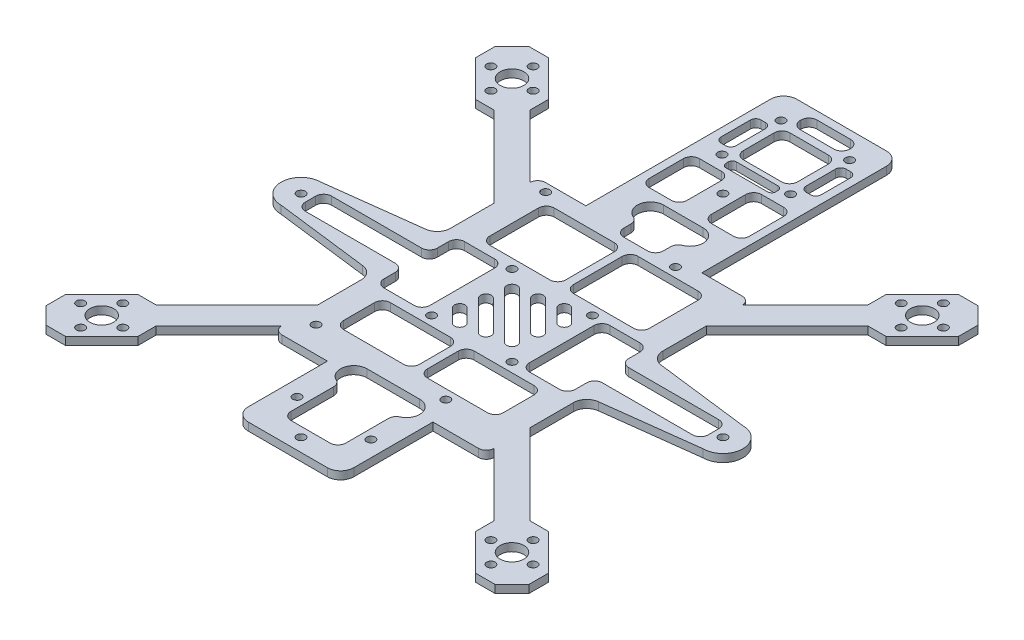
SolidWorks part; units mm, degrees
material "商用纯钛 (Ti-55) UNS R50550*"
ref_plane "前视基准面" through (0, 0, 0) normal (0, 0, 1) x (1, 0, 0)
ref_plane "上视基准面" through (0, 0, 0) normal (0, 1, 0) x (1, 0, 0)
ref_plane "右视基准面" through (0, 0, 0) normal (1, 0, 0) x (0, 0, -1)
other "Configuration Table"
sketch "草图1" plane through (0, 0, 0) normal (0, 1, 0) x (1, 0, 0)
  line L0 (-40.28, 0) -> (40.28, 0) construction
  line L1 (-40.28, -50) -> (40.28, -50)
  line L2 (-40.28, -50) -> (-40.28, -16.9164)
  line L3 (-40.28, 50) -> (40.28, 50)
  line L4 (40.28, -50) -> (40.28, -16.9164)
  line L5 (-40.28, -50) -> (40.28, 50) construction
  line L6 (-40.28, 50) -> (40.28, -50) construction
  line L7 (0, -50) -> (0, 50) construction
  line L8 (-40.28, -50) -> (-40.28, -85) construction
  line L9 (-40.28, -85) -> (40.28, -85) construction
  line L10 (40.28, -85) -> (40.28, -50) construction
  line L11 (0, -50) -> (0, -85) construction
  line L12 (-40.28, -67.5) -> (40.28, -67.5) construction
  line L13 (-20, -85) -> (20, -85)
  line L14 (20, -85) -> (20, -50)
  line L15 (-20, -85) -> (-20, -50)
  line L16 (44.6626, 11.9547) -> (80, 7.5578)
  line L17 (44.6626, -11.9547) -> (80, -7.5578)
  line L18 (-44.6626, -11.9547) -> (-80, -7.5578)
  line L19 (-44.6626, 11.9547) -> (-80, 7.5578)
  line L20 (40.28, 16.9164) -> (40.28, 50)
  line L21 (-40.28, 16.9164) -> (-40.28, 50)
  circle A0 centre (-34.12, 46.89) radius 1.6
  circle A1 centre (15.09, 46.89) radius 1.6
  circle A2 centre (15.09, -40.19) radius 1.6
  circle A3 centre (-34.12, -40.19) radius 1.6
  circle A5 centre (-15.25, 15.25) radius 1.6
  circle A6 centre (15.25, 15.25) radius 1.6
  circle A7 centre (15.25, -15.25) radius 1.6
  circle A8 centre (-15.25, -15.25) radius 1.6
  circle A9 centre (14, -67.5) radius 1.6
  circle A10 centre (-14, -67.5) radius 1.6
  circle A11 centre (80, 0) radius 7.5 construction
  circle A12 centre (-80, 0) radius 7.5 construction
  circle A14 centre (80, 0) radius 1.6
  circle A16 centre (-80, 0) radius 1.6
  arc A17 (80, 7.5578) -> (80, -7.5578) centre (80, 0) cw
  arc A18 (-80, 7.5578) -> (-80, -7.5578) centre (-80, 0) ccw
  arc A19 (44.6626, 11.9547) -> (40.28, 16.9164) centre (45.28, 16.9164) cw
  arc A20 (44.6626, -11.9547) -> (40.28, -16.9164) centre (45.28, -16.9164) ccw
  arc A21 (-44.6626, -11.9547) -> (-40.28, -16.9164) centre (-45.28, -16.9164) cw
  arc A22 (-44.6626, 11.9547) -> (-40.28, 16.9164) centre (-45.28, 16.9164) ccw
  point P0 (0, 0)
  point P19 (0, 0)
  point P22 (0, 0)
  point P40 (0, -85)
  point P62 (40.28, 12.5)
  point P65 (40.28, -12.5)
  point P68 (-40.28, -12.5)
  point P71 (-40.28, 12.5)
  dimension "D3" = 3.2
  dimension "D10" = 3.2
  dimension "D11" = 30.5
  dimension "D12" = 30.5
  dimension "D14" = 3.2
  dimension "D18" = 15
  dimension "D21" = 3.2
  dimension "D19" = 160
  dimension "D23" = 5
  dimension "D1" = 80.56
  dimension "D2" = 100
  dimension "D4" = 6.16
  dimension "D5" = 3.11
  dimension "D8" = 49.21
  dimension "D9" = 87.08
  dimension "D13" = 35
  dimension "D15" = 28
  dimension "D16" = 40
  dimension "D17" = 25
  dimension "D6" = 2
  dimension "D7" = 2
extrude "凸台-拉伸1" add sketch "草图1" along normal blind 3 contours L15 L13 L14 L1 A9 A10 | L1 L4 L3 L2 A6 A5 A3 A2 A1 A0 A7 A8 region at (0.0313, 0, 0.011) region at (0, 0, 67.5)
sketch "草图6" plane through (0, 0, 0) normal (0, 1, 0) x (1, 0, 0)
  line L0 (0, 0) -> (50000, 0) construction
  line L1 (0, 0) -> (0, 50000) construction
  line L2 (-77.7817, 77.7817) -> (77.7817, 77.7817) construction
  line L3 (77.7817, 77.7817) -> (77.7817, -77.7817) construction
  line L4 (69.7817, 77.7817) -> (85.7817, 77.7817) construction
  line L5 (77.7817, 69.7817) -> (77.7817, 85.7817) construction
  line L6 (-77.7817, -77.7817) -> (77.7817, 77.7817) construction
  line L7 (77.7817, 91.5317) -> (64.0317, 77.7817)
  line L8 (91.5317, 77.7817) -> (77.7817, 64.0317)
  line L9 (-70.9067, 64.0317) -> (-40.28, 33.405)
  line L10 (-91.5317, -91.5317) -> (88.3498, 88.3498) construction
  line L11 (-87.5951, 87.5951) -> (77.7817, -77.7817) construction
  line L12 (40.28, -50) -> (40.28, 50)
  line L13 (40.28, 50) -> (-40.28, 50)
  line L14 (-40.28, 50) -> (-40.28, -50)
  line L15 (-40.28, -50) -> (40.28, -50)
  line L16 (-77.7817, 64.0317) -> (-70.9067, 64.0317)
  line L17 (-91.5317, 77.7817) -> (-77.7817, 64.0317)
  line L18 (-91.5317, 77.7817) -> (-91.5317, 85.1678)
  line L19 (-85.1678, 91.5317) -> (-91.5317, 85.1678)
  line L20 (-77.7817, 91.5317) -> (-85.1678, 91.5317)
  line L21 (77.7817, 91.5317) -> (85.1678, 91.5317)
  line L22 (91.5317, 77.7817) -> (91.5317, 85.1678)
  line L23 (-77.7817, 91.5317) -> (-64.0317, 77.7817)
  line L24 (-64.0317, 77.7817) -> (-64.0317, 70.9067)
  line L25 (72.1249, 83.4386) -> (83.4386, 72.1249) construction
  line L26 (77.7817, 64.0317) -> (70.9067, 64.0317)
  line L27 (64.0317, 77.7817) -> (64.0317, 70.9067)
  line L28 (77.7817, 64.0317) -> (70.9067, 64.0317)
  line L29 (64.0317, 77.7817) -> (64.0317, 70.9067)
  line L30 (64.0317, 70.9067) -> (40.28, 47.155)
  line L31 (70.9067, 64.0317) -> (40.28, 33.405)
  line L32 (85.1678, 91.5317) -> (91.5317, 85.1678)
  line L33 (-64.0317, 70.9067) -> (-40.28, 47.155)
  line L34 (-64.0317, -70.9067) -> (-40.28, -47.155)
  line L35 (-64.0317, -77.7817) -> (-64.0317, -70.9067)
  line L36 (-77.7817, -91.5317) -> (-64.0317, -77.7817)
  line L37 (-77.7817, -91.5317) -> (-85.1678, -91.5317)
  line L38 (-85.1678, -91.5317) -> (-91.5317, -85.1678)
  line L39 (-91.5317, -77.7817) -> (-91.5317, -85.1678)
  line L40 (-91.5317, -77.7817) -> (-77.7817, -64.0317)
  line L41 (-77.7817, -64.0317) -> (-70.9067, -64.0317)
  line L42 (-70.9067, -64.0317) -> (-40.28, -33.405)
  line L43 (70.9067, -64.0317) -> (40.28, -33.405)
  line L44 (77.7817, -64.0317) -> (70.9067, -64.0317)
  line L45 (91.5317, -77.7817) -> (77.7817, -64.0317)
  line L46 (91.5317, -77.7817) -> (91.5317, -85.1678)
  line L47 (85.1678, -91.5317) -> (91.5317, -85.1678)
  line L48 (77.7817, -91.5317) -> (85.1678, -91.5317)
  line L49 (77.7817, -91.5317) -> (64.0317, -77.7817)
  line L50 (64.0317, -77.7817) -> (64.0317, -70.9067)
  line L51 (64.0317, -70.9067) -> (40.28, -47.155)
  circle A0 centre (-77.7817, 77.7817) radius 65.9 construction
  circle A1 centre (77.7817, 77.7817) radius 65.9 construction
  circle A2 centre (-77.7817, -77.7817) radius 65.9 construction
  circle A3 centre (77.7817, -77.7817) radius 65.9 construction
  circle A4 centre (0, 0) radius 110 construction
  circle A5 centre (77.7817, 77.7817) radius 8 construction
  circle A6 centre (77.7817, 85.7817) radius 1.6
  circle A7 centre (85.7817, 77.7817) radius 1.6
  circle A8 centre (77.7817, 69.7817) radius 1.6
  circle A9 centre (69.7817, 77.7817) radius 1.6
  circle A10 centre (77.7817, 77.7817) radius 13.75 construction
  circle A11 centre (-77.7817, 85.7817) radius 1.6
  circle A12 centre (-85.7817, 77.7817) radius 1.6
  circle A13 centre (-69.7817, 77.7817) radius 1.6
  circle A14 centre (-77.7817, 69.7817) radius 1.6
  circle A15 centre (-77.7817, -69.7817) radius 1.6
  circle A16 centre (-69.7817, -77.7817) radius 1.6
  circle A17 centre (-85.7817, -77.7817) radius 1.6
  circle A18 centre (-77.7817, -85.7817) radius 1.6
  circle A19 centre (77.7817, -85.7817) radius 1.6
  circle A20 centre (85.7817, -77.7817) radius 1.6
  circle A21 centre (69.7817, -77.7817) radius 1.6
  circle A22 centre (77.7817, -69.7817) radius 1.6
  point P18 (77.7817, 77.7817)
  point P21 (77.7817, 77.7817)
  point P24 (0, 0)
  point P31 (77.7817, 77.7817)
  point P77 (77.7817, 77.7817)
  dimension "D1" = 3.2
  dimension "D2" = 3.2
  dimension "D3" = 3.2
  dimension "D4" = 3.2
  dimension "D5" = 3.2
  dimension "D6" = 3.2
  dimension "D7" = 3.2
  dimension "D8" = 3.2
  dimension "D9" = 3.2
  dimension "D10" = 3.2
  dimension "D11" = 3.2
  dimension "D12" = 3.2
  dimension "D13" = 3.2
  dimension "D14" = 3.2
  dimension "D15" = 3.2
  dimension "D16" = 3.2
extrude "凸台-拉伸3" add sketch "草图6" along normal blind 3 contours L33 L24 L23 L20 L19 L18 L17 L16 L9 L14 A13 A11 A12 A14 | L32 L21 L7 L27 L30 L12 L31 L26 L8 L22 A9 A8 A7 A6 | L51 L50 L49 L48 L47 L46 L45 L44 L43 L12 A21 A19 A20 A22 | L42 L41 L40 L39 L38 L37 L36 L35 L34 L14 A18 A17 A16 A15 region at (67.5211, 0, -67.3959) region at (67.5211, 0, 67.3959) region at (-67.5211, 0, -67.3959) region at (-67.5211, 0, 67.3959)
sketch "草图7" plane through (0, 0, 0) normal (0, 1, 0) x (1, 0, 0)
  line L0 (-8.8388, 8.8388) -> (8.8388, -8.8388) construction
  line L1 (-15.25, -15.25) -> (15.25, -15.25) construction
  line L2 (-15.25, -15.25) -> (-15.25, 15.25) construction
  line L3 (-15.25, 15.25) -> (15.25, 15.25) construction
  line L4 (15.25, -15.25) -> (15.25, 15.25) construction
  line L5 (-15.25, -15.25) -> (15.25, 15.25) construction
  line L6 (-15.25, 15.25) -> (15.25, -15.25) construction
  line L7 (-7.4246, 10.253) -> (10.253, -7.4246)
  line L8 (-10.253, 7.4246) -> (7.4246, -10.253)
  line L9 (-0.7071, 10.6066) -> (10.6066, -0.7071) construction
  line L10 (0.7071, 12.0208) -> (12.0208, 0.7071)
  line L11 (-2.1213, 9.1924) -> (9.1924, -2.1213)
  line L12 (7.4246, 12.3744) -> (12.3744, 7.4246) construction
  line L13 (8.8388, 13.7886) -> (13.7886, 8.8388)
  line L14 (6.0104, 10.9602) -> (10.9602, 6.0104)
  line L15 (-12.3744, -7.4246) -> (-7.4246, -12.3744) construction
  line L16 (-13.7886, -8.8388) -> (-8.8388, -13.7886)
  line L17 (-10.9602, -6.0104) -> (-6.0104, -10.9602)
  line L18 (-10.6066, 0.7071) -> (0.7071, -10.6066) construction
  line L19 (-12.0208, -0.7071) -> (-0.7071, -12.0208)
  line L20 (-9.1924, 2.1213) -> (2.1213, -9.1924)
  line L21 (0, -50) -> (0, 50) construction
  line L22 (-40.28, 50) -> (40.28, 50) construction
  line L23 (-20, -50) -> (20, -50) construction
  line L24 (-10, -50) -> (10, -50) construction
  line L25 (-10, -45) -> (10, -45)
  line L26 (-10, -55) -> (10, -55)
  arc A0 (-7.4246, 10.253) -> (-10.253, 7.4246) centre (-8.8388, 8.8388) ccw
  arc A1 (7.4246, -10.253) -> (10.253, -7.4246) centre (8.8388, -8.8388) ccw
  arc A2 (0.7071, 12.0208) -> (-2.1213, 9.1924) centre (-0.7071, 10.6066) ccw
  arc A3 (9.1924, -2.1213) -> (12.0208, 0.7071) centre (10.6066, -0.7071) ccw
  arc A4 (8.8388, 13.7886) -> (6.0104, 10.9602) centre (7.4246, 12.3744) ccw
  arc A5 (10.9602, 6.0104) -> (13.7886, 8.8388) centre (12.3744, 7.4246) ccw
  arc A6 (-13.7886, -8.8388) -> (-10.9602, -6.0104) centre (-12.3744, -7.4246) cw
  arc A7 (-6.0104, -10.9602) -> (-8.8388, -13.7886) centre (-7.4246, -12.3744) cw
  arc A8 (-12.0208, -0.7071) -> (-9.1924, 2.1213) centre (-10.6066, 0.7071) cw
  arc A9 (2.1213, -9.1924) -> (-0.7071, -12.0208) centre (0.7071, -10.6066) cw
  arc A10 (-10, -45) -> (-10, -55) centre (-10, -50) ccw
  arc A11 (10, -55) -> (10, -45) centre (10, -50) ccw
  circle A12 centre (0, -80) radius 1.6
  point P0 (0, 0)
  point P9 (0, 0)
  point P16 (4.9497, 4.9497)
  point P21 (9.8995, 9.8995)
  point P31 (-9.8995, -9.8995)
  point P38 (-4.9497, -4.9497)
  point P48 (0, 0)
  point P51 (0, -50)
  point P53 (0, -50)
  dimension "D3" = 4
  dimension "D7" = 2
  dimension "D9" = 5
  dimension "D11" = 3.2
  dimension "D1" = 4
  dimension "D2" = 25
  dimension "D4" = 3
  dimension "D5" = 16
  dimension "D6" = 7
  dimension "D8" = 3
  dimension "D10" = 20
  dimension "D12" = 80
extrude "切除-拉伸5" cut sketch "草图7" along normal through all contours A7 L17 A6 L16 | A9 L20 A8 L19 | L8 A1 L7 A0 | L11 A3 L10 A2 | L14 A5 L13 A4 | L26 A11 L25 A10 | A12 region at (0, 0, 0) region at (4.9497, 0, -4.9497) region at (9.8995, 0, -9.8995) region at (-9.8995, 0, 9.8995) region at (-4.9497, 0, 4.9497) region at (0, 0, 50) region at (0, 0, 80)
sketch "草图8" plane through (0, 0, 0) normal (0, 1, 0) x (1, 0, 0)
  line L0 (0, 0) -> (0, 87.5) construction
  line L1 (-40.28, 50) -> (40.28, 50) construction
  line L2 (-22, 125) -> (22, 125)
  line L3 (-22, 125) -> (-22, 50)
  line L4 (-22, 50) -> (22, 50)
  line L5 (22, 125) -> (22, 50)
  line L6 (-22, 125) -> (22, 50) construction
  line L7 (-22, 50) -> (22, 125) construction
  line L8 (13, 50) -> (13, 125) construction
  line L9 (-7.5, 60) -> (7.5, 60) construction
  line L10 (-7.5, 65) -> (7.5, 65)
  line L11 (-7.5, 55) -> (7.5, 55)
  circle A0 centre (13, 115) radius 1.6
  circle A1 centre (-13, 115) radius 1.6
  circle A2 centre (13, 92.63) radius 1.6
  circle A3 centre (-13, 92.63) radius 1.6
  arc A4 (-7.5, 65) -> (-7.5, 55) centre (-7.5, 60) ccw
  arc A5 (7.5, 55) -> (7.5, 65) centre (7.5, 60) ccw
  circle A6 centre (0, 80) radius 1.6
  point P21 (0, 60)
  dimension "D4" = 3.2
  dimension "D6" = 3.2
  dimension "D9" = 5
  dimension "D11" = 3.2
  dimension "D12" = 80
  dimension "D1" = 75
  dimension "D2" = 44
  dimension "D3" = 9
  dimension "D5" = 10
  dimension "D7" = 22.37
  dimension "D8" = 15
  dimension "D10" = 5
extrude "凸台-拉伸4" add sketch "草图8" along normal blind 3
fillet "圆角1" radius 5 4 edges at (-22, 1.5, -125) (22, 1.5, -125) (20, 1.5, 85) (-20, 1.5, 85)
fillet "圆角2" radius 3 4 edges at (-40.28, 1.5, 50) (40.28, 1.5, 50) (40.28, 1.5, -50) (-40.28, 1.5, -50)
sketch "草图9" plane through (0, 0, 0) normal (0, 1, 0) x (1, 0, 0)
  line L0 (-87.5578, 0) -> (87.5578, 0) construction
  line L1 (0, -125) -> (0, 125) construction
  line L2 (17, 125) -> (-17, 125) construction
  line L3 (-44.6626, 11.9547) -> (-80, 7.5578) construction
  line L4 (-7.2711, 94.9779) -> (7.2711, 94.9779)
  line L5 (-10.2711, 97.9779) -> (-10.2711, 109.6521)
  line L6 (-7.2711, 112.6521) -> (7.2711, 112.6521)
  line L7 (10.2711, 97.9779) -> (10.2711, 109.6521)
  line L8 (-10.2711, 94.9779) -> (10.2711, 112.6521) construction
  line L9 (-10.2711, 112.6521) -> (10.2711, 94.9779) construction
  line L10 (-27.28, 43.2936) -> (-4.5, 43.2936)
  line L11 (-30.28, 40.2936) -> (-30.28, 21.85)
  line L12 (-27.28, 18.85) -> (-4.5, 18.85)
  line L13 (30.28, 40.2936) -> (30.28, 21.85)
  line L14 (-33.96, 43.2936) -> (15.25, 18.85) construction
  line L15 (-30.28, 18.85) -> (15.25, 43.2936) construction
  line L16 (-73.4, 4.9826) -> (-39.28, 4.9826)
  line L17 (-76.4, 1.9826) -> (-76.4, -1.9826)
  line L18 (-73.4, -4.9826) -> (-39.28, -4.9826)
  line L19 (-18.85, 4.9826) -> (-18.85, -1.9826)
  line L20 (-76.4, 4.9826) -> (-18.85, -4.9826) construction
  line L21 (-76.4, -4.9826) -> (-18.85, 4.9826) construction
  line L22 (18.85, 1.9826) -> (18.85, -1.9826)
  line L23 (73.4, -4.9826) -> (39.28, -4.9826)
  line L24 (76.4, 1.9826) -> (76.4, -1.9826)
  line L25 (73.4, 4.9826) -> (39.28, 4.9826)
  line L26 (40.28, 16.9164) -> (40.28, 33.405) construction
  line L27 (-27.28, -18.85) -> (-4.5, -18.85)
  line L28 (-30.28, -21.85) -> (-30.28, -33.5936)
  line L29 (-27.28, -36.5936) -> (-4.5, -36.5936)
  line L30 (30.28, -21.85) -> (30.28, -33.5936)
  line L31 (-30.28, -18.85) -> (19.0555, -35.5436) construction
  line L32 (-30.28, -36.5936) -> (15.25, -18.85) construction
  line L34 (-10.4, -54.984) -> (-10.4, -73.4)
  line L35 (-7.4, -76.4) -> (7.4, -76.4)
  line L36 (10.4, -54.984) -> (10.4, -73.4)
  line L37 (-10.4, -54.984) -> (10.4, -76.4) construction
  line L38 (-10.4, -76.4) -> (10.4, -54.984) construction
  line L39 (40.28, -33.405) -> (40.28, -16.9164) construction
  line L40 (22, 50) -> (22, 120) construction
  line L41 (-10.4, -54.984) -> (10.4, -54.984)
  line L42 (69.7817, 77.7817) -> (85.7817, 77.7817) construction
  line L43 (77.7817, 85.7817) -> (77.7817, 69.7817) construction
  line L44 (-1.5, 40.2936) -> (-1.5, 21.85)
  line L45 (1.5, 40.2936) -> (1.5, 21.85)
  line L46 (4.5, 43.2936) -> (27.28, 43.2936)
  line L47 (4.5, 18.85) -> (27.28, 18.85)
  line L48 (-1.5, -21.85) -> (-1.5, -33.5936)
  line L49 (1.5, -21.85) -> (1.5, -33.5936)
  line L50 (4.5, -18.85) -> (27.28, -18.85)
  line L51 (4.5, -36.5936) -> (27.28, -36.5936)
  line L52 (7.6, 87.03) -> (16, 87.03)
  line L53 (4.6, 84.03) -> (4.6, 71)
  line L54 (7.6, 68) -> (16, 68)
  line L55 (19, 84.03) -> (19, 71)
  line L56 (4.6, 87.03) -> (19, 68) construction
  line L57 (4.6, 68) -> (19, 87.03) construction
  line L58 (7.5, 65) -> (-7.5, 65) construction
  line L59 (-19, 84.03) -> (-19, 71)
  line L60 (-7.6, 68) -> (-16, 68)
  line L61 (-4.6, 84.03) -> (-4.6, 71)
  line L62 (-7.6, 87.03) -> (-16, 87.03)
  line L63 (18.85, 1.9826) -> (18.85, 12.25)
  line L64 (21.85, 15.25) -> (33.28, 15.25)
  line L65 (36.28, 12.25) -> (36.28, 7.9826)
  line L66 (-36.28, 12.25) -> (-36.28, 7.9826)
  line L67 (-21.85, 15.25) -> (-33.28, 15.25)
  line L68 (-18.85, 4.9826) -> (-18.85, 12.25)
  line L69 (36.28, -12.25) -> (36.28, -7.9826)
  line L70 (21.85, -15.25) -> (33.28, -15.25)
  line L71 (18.85, -1.9826) -> (18.85, -12.25)
  line L72 (-18.85, -1.9826) -> (-18.85, -12.25)
  line L73 (-21.85, -15.25) -> (-33.28, -15.25)
  line L74 (-36.28, -12.25) -> (-36.28, -7.9826)
  line L75 (-15.2711, 96.23) -> (-17, 96.23)
  line L76 (-6.4, 122) -> (6.4, 122)
  line L77 (-9.4, 119) -> (-9.4, 118.6521)
  line L78 (-6.4, 115.6521) -> (6.4, 115.6521)
  line L79 (9.4, 119) -> (9.4, 118.6521)
  line L80 (-9.4, 122) -> (9.4, 115.6521) construction
  line L81 (-9.4, 115.6521) -> (9.4, 122) construction
  line L82 (15.2711, 111.4) -> (17, 111.4)
  line L83 (13.2711, 109.4) -> (13.2711, 98.23)
  line L84 (15.2711, 96.23) -> (17, 96.23)
  line L85 (19, 109.4) -> (19, 98.23)
  line L86 (13.2711, 111.4) -> (19, 96.23) construction
  line L87 (13.2711, 96.23) -> (19, 111.4) construction
  line L88 (-19, 109.4) -> (-19, 98.23)
  line L89 (-13.2711, 109.4) -> (-13.2711, 98.23)
  line L90 (-15.2711, 111.4) -> (-17, 111.4)
  line L91 (-7.5, 55) -> (-7.5, 49.89)
  line L92 (-7.9, 92.9779) -> (7.9, 92.9779)
  line L93 (-9.4, 91.4779) -> (-9.4, 90.53)
  line L94 (-7.9, 89.03) -> (7.9, 89.03)
  line L95 (9.4, 91.4779) -> (9.4, 90.53)
  line L96 (-9.4, 92.9779) -> (9.4, 89.03) construction
  line L97 (-9.4, 89.03) -> (9.4, 92.9779) construction
  line L98 (-4.5, 46.89) -> (4.5, 46.89)
  line L99 (7.5, 55) -> (7.5, 49.89)
  line L100 (-7.5, 55) -> (7.5, 55)
  arc A0 (80, -7.5578) -> (80, 7.5578) centre (80, 0) ccw construction
  circle A1 centre (13, 115) radius 3.6 construction
  circle A2 centre (13, 115) radius 1.6 construction
  circle A3 centre (13, 92.63) radius 3.6 construction
  circle A4 centre (13, 92.63) radius 1.6 construction
  arc A5 (7.2711, 94.9779) -> (10.2711, 97.9779) centre (7.2711, 97.9779) ccw
  arc A6 (7.2711, 112.6521) -> (10.2711, 109.6521) centre (7.2711, 109.6521) cw
  arc A7 (-7.2711, 94.9779) -> (-10.2711, 97.9779) centre (-7.2711, 97.9779) cw
  arc A8 (-10.2711, 109.6521) -> (-7.2711, 112.6521) centre (-7.2711, 109.6521) cw
  circle A9 centre (15.09, 46.89) radius 3.6 construction
  circle A10 centre (15.09, 46.89) radius 1.6 construction
  circle A11 centre (-34.12, 46.89) radius 3.6 construction
  circle A12 centre (-34.12, 46.89) radius 1.6 construction
  circle A13 centre (15.25, 15.25) radius 3.6 construction
  circle A14 centre (15.25, 15.25) radius 1.6 construction
  circle A15 centre (-15.25, -15.25) radius 1.6 construction
  arc A16 (27.28, -18.85) -> (30.28, -21.85) centre (27.28, -21.85) cw
  circle A17 centre (-15.25, 15.25) radius 1.6 construction
  arc A18 (27.28, 43.2936) -> (30.28, 40.2936) centre (27.28, 40.2936) cw
  arc A19 (27.28, 18.85) -> (30.28, 21.85) centre (27.28, 21.85) ccw
  arc A20 (-30.28, 21.85) -> (-27.28, 18.85) centre (-27.28, 21.85) ccw
  arc A21 (-27.28, 43.2936) -> (-30.28, 40.2936) centre (-27.28, 40.2936) ccw
  arc A22 (27.28, -36.5936) -> (30.28, -33.5936) centre (27.28, -33.5936) ccw
  arc A23 (-30.28, -33.5936) -> (-27.28, -36.5936) centre (-27.28, -33.5936) ccw
  circle A24 centre (-80, 0) radius 1.6 construction
  arc A27 (-76.4, -1.9826) -> (-73.4, -4.9826) centre (-73.4, -1.9826) ccw
  arc A28 (-73.4, 4.9826) -> (-76.4, 1.9826) centre (-73.4, 1.9826) ccw
  arc A31 (76.4, -1.9826) -> (73.4, -4.9826) centre (73.4, -1.9826) cw
  arc A32 (73.4, 4.9826) -> (76.4, 1.9826) centre (73.4, 1.9826) cw
  circle A33 centre (15.09, -40.19) radius 3.6 construction
  circle A34 centre (-34.12, -40.19) radius 3.6 construction
  circle A35 centre (15.25, -15.25) radius 3.6 construction
  circle A36 centre (15.25, -15.25) radius 1.6 construction
  circle A37 centre (15.09, -40.19) radius 1.6 construction
  arc A38 (-27.28, -18.85) -> (-30.28, -21.85) centre (-27.28, -21.85) ccw
  circle A39 centre (-34.12, -40.19) radius 1.6 construction
  circle A40 centre (77.7817, 77.7817) radius 4.5
  circle A41 centre (77.7817, -77.7817) radius 4.5
  circle A42 centre (14, -67.5) radius 1.6 construction
  circle A43 centre (-77.7817, -77.7817) radius 4.5
  circle A44 centre (-77.7817, 77.7817) radius 4.5
  circle A45 centre (-14, -67.5) radius 1.6 construction
  arc A46 (-10, -45) -> (-10, -55) centre (-10, -50) ccw construction
  circle A47 centre (0, -80) radius 1.6 construction
  arc A48 (7.4, -76.4) -> (10.4, -73.4) centre (7.4, -73.4) ccw
  arc A49 (-10.4, -73.4) -> (-7.4, -76.4) centre (-7.4, -73.4) ccw
  arc A50 (1.5, 40.2936) -> (4.5, 43.2936) centre (4.5, 40.2936) cw
  arc A51 (1.5, 21.85) -> (4.5, 18.85) centre (4.5, 21.85) ccw
  arc A52 (-1.5, 21.85) -> (-4.5, 18.85) centre (-4.5, 21.85) cw
  arc A53 (-1.5, 40.2936) -> (-4.5, 43.2936) centre (-4.5, 40.2936) ccw
  arc A54 (1.5, -21.85) -> (4.5, -18.85) centre (4.5, -21.85) cw
  arc A55 (1.5, -33.5936) -> (4.5, -36.5936) centre (4.5, -33.5936) ccw
  arc A56 (-1.5, -33.5936) -> (-4.5, -36.5936) centre (-4.5, -33.5936) cw
  arc A57 (-1.5, -21.85) -> (-4.5, -18.85) centre (-4.5, -21.85) ccw
  arc A58 (-36.28, -7.9826) -> (-39.28, -4.9826) centre (-39.28, -7.9826) ccw
  circle A59 centre (0, 80) radius 1.6 construction
  arc A60 (4.6, 71) -> (7.6, 68) centre (7.6, 71) ccw
  arc A61 (16, 68) -> (19, 71) centre (16, 71) ccw
  arc A62 (16, 87.03) -> (19, 84.03) centre (16, 84.03) cw
  arc A63 (7.6, 87.03) -> (4.6, 84.03) centre (7.6, 84.03) ccw
  arc A64 (-16, 87.03) -> (-19, 84.03) centre (-16, 84.03) ccw
  arc A65 (-16, 68) -> (-19, 71) centre (-16, 71) cw
  arc A66 (-4.6, 71) -> (-7.6, 68) centre (-7.6, 71) cw
  arc A67 (-7.6, 87.03) -> (-4.6, 84.03) centre (-7.6, 84.03) cw
  arc A68 (33.28, 15.25) -> (36.28, 12.25) centre (33.28, 12.25) cw
  arc A69 (18.85, 12.25) -> (21.85, 15.25) centre (21.85, 12.25) cw
  arc A70 (-33.28, 15.25) -> (-36.28, 12.25) centre (-33.28, 12.25) ccw
  arc A71 (-18.85, 12.25) -> (-21.85, 15.25) centre (-21.85, 12.25) ccw
  arc A72 (33.28, -15.25) -> (36.28, -12.25) centre (33.28, -12.25) ccw
  arc A73 (18.85, -12.25) -> (21.85, -15.25) centre (21.85, -12.25) ccw
  arc A74 (-18.85, -12.25) -> (-21.85, -15.25) centre (-21.85, -12.25) cw
  arc A75 (-33.28, -15.25) -> (-36.28, -12.25) centre (-33.28, -12.25) cw
  arc A76 (-36.28, 7.9826) -> (-39.28, 4.9826) centre (-39.28, 7.9826) cw
  arc A77 (36.28, -7.9826) -> (39.28, -4.9826) centre (39.28, -7.9826) cw
  arc A78 (36.28, 7.9826) -> (39.28, 4.9826) centre (39.28, 7.9826) ccw
  arc A79 (6.4, 115.6521) -> (9.4, 118.6521) centre (6.4, 118.6521) ccw
  arc A80 (6.4, 122) -> (9.4, 119) centre (6.4, 119) cw
  arc A81 (-9.4, 118.6521) -> (-6.4, 115.6521) centre (-6.4, 118.6521) ccw
  arc A82 (-6.4, 122) -> (-9.4, 119) centre (-6.4, 119) ccw
  arc A83 (17, 96.23) -> (19, 98.23) centre (17, 98.23) ccw
  arc A84 (13.2711, 98.23) -> (15.2711, 96.23) centre (15.2711, 98.23) ccw
  arc A85 (17, 111.4) -> (19, 109.4) centre (17, 109.4) cw
  arc A86 (15.2711, 111.4) -> (13.2711, 109.4) centre (15.2711, 109.4) ccw
  arc A87 (-17, 96.23) -> (-19, 98.23) centre (-17, 98.23) cw
  arc A88 (-13.2711, 98.23) -> (-15.2711, 96.23) centre (-15.2711, 98.23) cw
  arc A89 (-17, 111.4) -> (-19, 109.4) centre (-17, 109.4) ccw
  arc A90 (-15.2711, 111.4) -> (-13.2711, 109.4) centre (-15.2711, 109.4) cw
  arc A91 (7.9, 92.9779) -> (9.4, 91.4779) centre (7.9, 91.4779) cw
  arc A92 (7.9, 89.03) -> (9.4, 90.53) centre (7.9, 90.53) ccw
  arc A93 (-9.4, 90.53) -> (-7.9, 89.03) centre (-7.9, 90.53) ccw
  arc A94 (-7.9, 92.9779) -> (-9.4, 91.4779) centre (-7.9, 91.4779) ccw
  arc A95 (7.5, 49.89) -> (4.5, 46.89) centre (4.5, 49.89) cw
  arc A96 (-7.5, 49.89) -> (-4.5, 46.89) centre (-4.5, 49.89) ccw
  point P0 (0, 103.815)
  point P7 (0, 0)
  point P13 (0, 0)
  point P49 (-8.3993, 30.597)
  point P80 (-47.625, 0)
  point P88 (-36.28, -4.9826)
  point P100 (-36.28, 4.9826)
  point P111 (-5.9097, -27.0962)
  point P147 (0, -65.692)
  point P182 (0, 0)
  point P187 (1.5, 43.2936)
  point P190 (1.5, 18.85)
  point P193 (-1.5, 18.85)
  point P196 (-1.5, 43.2936)
  point P203 (1.5, -18.85)
  point P206 (1.5, -36.5936)
  point P209 (-1.5, -36.5936)
  point P212 (-1.5, -18.85)
  point P217 (11.8, 77.515)
  point P278 (36.28, -4.9826)
  point P281 (36.28, 4.9826)
  point P283 (0, 118.826)
  point P300 (16.1355, 103.815)
  point P330 (0, 91.004)
  point P336 (0, 46.89)
  point P350 (7.5, 46.89)
  point P353 (-7.5, 46.89)
  dimension "D1" = 2
  dimension "D2" = 2
  dimension "D3" = 3
  dimension "D4" = 2
  dimension "D5" = 2
  dimension "D6" = 2
  dimension "D8" = 10
  dimension "D12" = 3
  dimension "D13" = 2
  dimension "D14" = 2
  dimension "D15" = 2
  dimension "D16" = 2
  dimension "D17" = 3
  dimension "D21" = 3
  dimension "D23" = 9
  dimension "D25" = 3
  dimension "D27" = 3
  dimension "D33" = 3
  dimension "D35" = 3
  dimension "D38" = 3
  dimension "D41" = 2
  dimension "D44" = 1.5
  dimension "D45" = 3
  dimension "D7" = 2
  dimension "D9" = 2
  dimension "D10" = 2
  dimension "D11" = 3
  dimension "D18" = 2
  dimension "D19" = 2
  dimension "D20" = 2
  dimension "D22" = 10
  dimension "D26" = 3
  dimension "D28" = 3
  dimension "D29" = 3
  dimension "D30" = 3
  dimension "D31" = 2
  dimension "D32" = 3
  dimension "D34" = 4
  dimension "D36" = 3
  dimension "D37" = 3
  dimension "D39" = 3
  dimension "D40" = 3
  dimension "D42" = 2
  dimension "D43" = 2
  dimension "D24" = 4
extrude "切除-拉伸6" cut sketch "草图9" along normal through all
fillet "圆角3" radius 3 4 edges at (10.4, 1.5, 54.984) (-10.4, 1.5, 54.984) (7.5, 1.5, -55) (-7.5, 1.5, -55)
